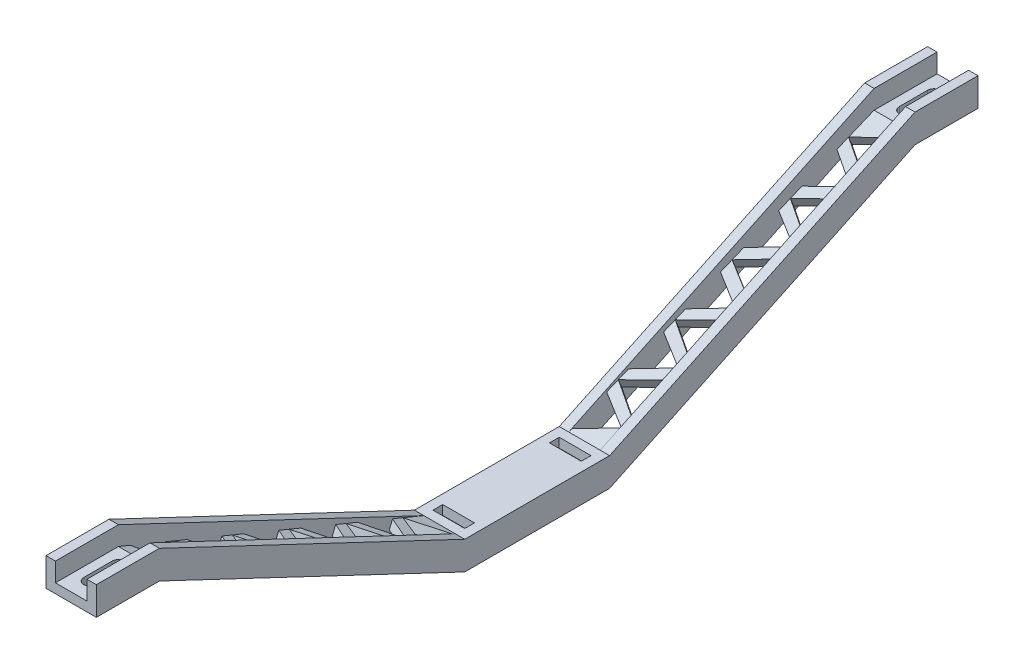
SolidWorks part; units mm, degrees
ref_plane "Front Plane" through (0, 0, 0) normal (0, 0, 1) x (1, 0, 0)
ref_plane "Top Plane" through (0, 0, 0) normal (0, 1, 0) x (1, 0, 0)
ref_plane "Right Plane" through (0, 0, 0) normal (1, 0, 0) x (0, 0, -1)
sketch "BaseSketch" plane through (0, 0, 0) normal (0, 1, 0) x (1, 0, 0)
  line L1 (-8, 150) -> (8, 150)
  line L2 (-8, 150) -> (-8, -150)
  line L3 (-8, -150) -> (8, -150)
  line L4 (8, 150) -> (8, -150)
  line L5 (-8, 150) -> (8, -150) construction
  line L6 (-8, -150) -> (8, 150) construction
  point P0 (0, 0)
  dimension "D1" = 300
  dimension "D2" = 16
extrude "Base" add sketch "BaseSketch" along normal blind 46
sketch "ShapeSketch" plane through (8, 0, 0) normal (1, 0, 0) x (0, 0, -1)
  line L0 (0, 0) -> (0, 3) construction
  line L1 (-23, 3) -> (23, 3)
  line L2 (120, 46) -> (120, 43) construction
  line L4 (-150, 46) -> (150, 46) construction
  line L6 (23, 3) -> (120, 3) construction
  line L7 (23, 3) -> (120, 43)
  line L8 (120, 43) -> (150, 43)
  line L9 (150, 46) -> (150, 0) construction
  line L10 (-23, 3) -> (-120, 3) construction
  line L11 (-120, 46) -> (-120, 43) construction
  line L12 (-23, 3) -> (-120, 43)
  line L13 (-120, 43) -> (-150, 43)
  line L14 (-150, 46) -> (-150, 0) construction
  line L15 (-150, 43) -> (-150, 46)
  line L16 (-150, 46) -> (-120, 46)
  line L17 (-23, 3) -> (-23, 6) construction
  line L18 (-23, 6) -> (23, 6)
  line L19 (23, 3) -> (23, 6) construction
  line L20 (150, 43) -> (150, 46)
  line L21 (150, 46) -> (120, 46)
  line L22 (23, 6) -> (120, 46)
  line L23 (-23, 6) -> (-120, 46)
  point P6 (0, 3)
  dimension "D1" = 3
  dimension "D2" = 46
  dimension "D3" = 97
  dimension "D4" = 3
  dimension "D5" = 30
  dimension "D6" = 97
  dimension "D7" = 3
  dimension "D8" = 30
  dimension "D9" = 3
extrude "Shape" cut sketch "ShapeSketch" against normal through all flip side to cut
sketch "SupportSketch" plane through (-8, 0, 0) normal (-1, 0, 0) x (0, 0, 1)
  line L1 (-150, 52) -> (-150, 43)
  line L5 (-150, 43) -> (-120, 43)
  line L9 (23, 3) -> (23, -3) construction
  line L10 (-23, 3) -> (-23, -3) construction
  line L11 (-120, 43) -> (-23, -3)
  line L12 (23, -3) -> (120, 43)
  line L13 (120, 46) -> (120, 52) construction
  line L15 (150, 46) -> (150, 52) construction
  line L20 (-120, 46) -> (-120, 52) construction
  line L21 (-150, 46) -> (-150, 52) construction
  line L24 (23, -3) -> (-23, -3)
  line L28 (-150, 52) -> (-120, 52)
  line L32 (120, 52) -> (150, 52)
  line L34 (120, 43) -> (150, 43)
  line L35 (-120, 52) -> (-23, 6)
  line L36 (-23, 6) -> (23, 6)
  line L37 (23, 6) -> (120, 52)
  line L38 (150, 43) -> (150, 52)
  dimension "D3" = 6
  dimension "D4" = 6
extrude "SupportR" add sketch "SupportSketch" against normal blind 3 from surface starting at face at (-8, 31.1667, 0)
extrude "SupportL" add sketch "SupportSketch<3>" along normal blind 3 from surface starting at face at (8, 31.1667, 0)
sketch "SupportSketch<3>" plane through (-8, 0, 0) normal (-1, 0, 0) x (0, 0, 1) same geometry as "SupportSketch"
sketch "ConnectionCenterSketch" plane through (0, 6, 0) normal (0, 1, 0) x (1, 0, 0)
  line L1 (0, -18.5) -> (0, 18.5) construction
  line L3 (-5.05, -20.05) -> (5.05, -20.05)
  line L4 (-5.05, -20.05) -> (-5.05, -16.95)
  line L5 (-5.05, -16.95) -> (5.05, -16.95)
  line L6 (5.05, -20.05) -> (5.05, -16.95)
  line L7 (-5.05, -20.05) -> (5.05, -16.95) construction
  line L8 (-5.05, -16.95) -> (5.05, -20.05) construction
  line L9 (-5.05, 16.95) -> (5.05, 16.95)
  line L10 (-5.05, 16.95) -> (-5.05, 20.05)
  line L11 (-5.05, 20.05) -> (5.05, 20.05)
  line L12 (5.05, 16.95) -> (5.05, 20.05)
  line L13 (-5.05, 16.95) -> (5.05, 20.05) construction
  line L14 (-5.05, 20.05) -> (5.05, 16.95) construction
  point P4 (0, 0)
  dimension "D1" = 37
  dimension "D2" = 3.1
  dimension "D3" = 10.1
extrude "ConnectionCenter" cut sketch "ConnectionCenterSketch" against normal through all
sketch "WeightLSketch" plane through (0, -2.9781, 1.2281) normal (0, 0.9245, -0.3812) x (1, 0, 0)
  line L0 (-5, -124.4742) -> (-5, -112.4742)
  line L1 (-5, -130.7616) -> (-5, -23.5504) construction
  line L2 (-5, -23.5504) -> (-5, -128.4742) construction
  line L3 (-5, -112.4742) -> (5, -118.7007)
  line L4 (5, -23.5504) -> (5, -128.4742) construction
  line L5 (5, -118.7007) -> (-5, -124.4742)
  line L6 (-5, -128.4742) -> (5, -128.4742) construction
  line L7 (5, -114.7007) -> (5, -102.7007)
  line L8 (5, -130.7616) -> (5, -23.5504) construction
  line L9 (5, -102.7007) -> (-5, -108.9272)
  line L10 (-5, -108.9272) -> (5, -114.7007)
  line L20 (-5, -104.9272) -> (-5, -92.9272)
  line L21 (-5, -104.9272) -> (5, -99.1537)
  line L22 (5, -99.1537) -> (-5, -92.9272)
  line L23 (5, -95.1537) -> (5, -83.1537)
  line L24 (5, -83.1537) -> (-5, -89.3802)
  line L25 (-5, -89.3802) -> (5, -95.1537)
  line L28 (5, -79.6067) -> (-5, -85.3802)
  line L29 (5, -75.6067) -> (5, -63.6067)
  line L30 (5, -63.6067) -> (-5, -69.8332)
  line L31 (-5, -69.8332) -> (5, -75.6067)
  line L32 (-5, -46.2862) -> (-5, -34.2862)
  line L33 (-5, -34.2862) -> (5, -40.5127)
  line L34 (5, -40.5127) -> (-5, -46.2862)
  line L35 (-5, -85.3802) -> (-5, -73.3802)
  line L36 (-5, -73.3802) -> (5, -79.6067)
  line L37 (-5, -65.8332) -> (-5, -53.8332)
  line L38 (-5, -53.8332) -> (5, -60.0597)
  line L39 (5, -60.0597) -> (-5, -65.8332)
  line L40 (5, -56.0597) -> (5, -44.0597)
  line L41 (5, -44.0597) -> (-5, -50.2862)
  line L42 (-5, -50.2862) -> (5, -56.0597)
  line L43 (5, -36.5127) -> (5, -24.5127)
  line L44 (5, -24.5127) -> (-5, -30.7392)
  line L45 (-5, -30.7392) -> (5, -36.5127)
  dimension "D1" = 12
  dimension "D2" = 60
  dimension "D3" = 4
  dimension "D4" = 4
  dimension "D5" = 12
  dimension "D6" = 60
  dimension "D7" = 4
  dimension "D8" = 12
  dimension "D9" = 60
  dimension "D10" = 4
  dimension "D11" = 60
  dimension "D12" = 12
  dimension "D13" = 4
  dimension "D14" = 12
  dimension "D15" = 60
  dimension "D16" = 4
  dimension "D17" = 12
  dimension "D18" = 60
  dimension "D19" = 4
  dimension "D20" = 12
  dimension "D21" = 60
  dimension "D22" = 4
  dimension "D23" = 60
  dimension "D24" = 12
  dimension "D25" = 4
  dimension "D26" = 60
  dimension "D27" = 12
  dimension "D28" = 4
  dimension "D29" = 12
  dimension "D30" = 60
extrude "WeightL" cut sketch "WeightLSketch" against normal through all
sketch "WeightRSketch" plane through (0, -2.9781, -1.2281) normal (0, 0.9245, 0.3812) x (1, 0, 0)
  line L0 (5, 125.4742) -> (5, 113.4742)
  line L1 (5, 23.5504) -> (5, 130.7616) construction
  line L2 (5, 128.4742) -> (5, 23.5504) construction
  line L3 (5, 113.4742) -> (-5, 119.7007)
  line L4 (-5, 23.5504) -> (-5, 130.7616) construction
  line L5 (-5, 119.7007) -> (5, 125.4742)
  line L6 (-5, 115.7007) -> (-5, 103.7007)
  line L7 (-5, 103.7007) -> (5, 109.4742)
  line L8 (5, 109.4742) -> (-5, 115.7007)
  line L9 (5, 105.4742) -> (5, 93.4742)
  line L10 (5, 93.4742) -> (-5, 99.7007)
  line L11 (-5, 99.7007) -> (5, 105.4742)
  line L12 (-5, 95.7007) -> (-5, 83.7007)
  line L13 (-5, 83.7007) -> (5, 89.9272)
  line L14 (5, 89.9272) -> (-5, 95.7007)
  line L15 (5, 85.9272) -> (5, 73.9272)
  line L16 (5, 73.9272) -> (-5, 79.7007)
  line L17 (-5, 79.7007) -> (5, 85.9272)
  line L18 (-5, 75.7007) -> (-5, 63.7007)
  line L19 (-5, 128.4742) -> (-5, 23.5504) construction
  line L20 (-5, 63.7007) -> (5, 69.9272)
  line L21 (5, 69.9272) -> (-5, 75.7007)
  line L22 (5, 65.9272) -> (5, 53.9272)
  line L23 (5, 53.9272) -> (-5, 60.1537)
  line L24 (-5, 60.1537) -> (5, 65.9272)
  line L25 (-5, 56.1537) -> (-5, 44.1537)
  line L26 (-5, 44.1537) -> (5, 50.3802)
  line L27 (5, 50.3802) -> (-5, 56.1537)
  line L28 (5, 46.3802) -> (5, 34.3802)
  line L29 (5, 34.3802) -> (-5, 40.6067)
  line L30 (-5, 40.6067) -> (5, 46.3802)
  line L31 (-5, 36.6067) -> (-5, 24.6067)
  line L32 (-5, 36.6067) -> (5, 30.8332)
  line L33 (5, 30.8332) -> (-5, 24.6067)
  dimension "D1" = 3
  dimension "D2" = 12
  dimension "D3" = 60
  dimension "D4" = 60
  dimension "D5" = 4
  dimension "D6" = 12
  dimension "D7" = 4
  dimension "D8" = 12
  dimension "D9" = 60
  dimension "D10" = 4
  dimension "D11" = 12
  dimension "D12" = 60
  dimension "D13" = 4
  dimension "D14" = 12
  dimension "D15" = 60
  dimension "D16" = 4
  dimension "D17" = 12
  dimension "D18" = 60
  dimension "D19" = 4
  dimension "D20" = 12
  dimension "D21" = 60
  dimension "D22" = 4
  dimension "D23" = 60
  dimension "D24" = 12
  dimension "D25" = 4
  dimension "D26" = 12
  dimension "D27" = 60
  dimension "D28" = 4
  dimension "D29" = 12
  dimension "D30" = 60
extrude "WeightR" cut sketch "WeightRSketch" against normal through all
sketch "ConnectionEndSketch" plane through (0, 46, 0) normal (0, 1, 0) x (1, 0, 0)
  line L0 (0, -150) -> (0, -134) construction
  line L3 (-5, -150) -> (5, -150) construction
  line L4 (0, -120) -> (0, -125) construction
  line L7 (0, 150) -> (0, 134) construction
  line L8 (5, 150) -> (-5, 150) construction
  line L9 (0, 120) -> (0, 125) construction
  line L10 (-5, 120) -> (5, 120) construction
  line L11 (0, 134) -> (0, 125) construction
  line L12 (2, 134) -> (2, 125)
  line L13 (-2, 134) -> (-2, 125)
  line L14 (-5, -120) -> (5, -120) construction
  line L15 (0, -134) -> (0, -125) construction
  line L16 (-2, -134) -> (-2, -125)
  line L17 (2, -134) -> (2, -125)
  arc A2 (2, 134) -> (-2, 134) centre (0, 134) ccw
  arc A3 (-2, 125) -> (2, 125) centre (0, 125) ccw
  arc A4 (-2, -134) -> (2, -134) centre (0, -134) ccw
  arc A5 (2, -125) -> (-2, -125) centre (0, -125) ccw
  point P8 (0, -129.5)
  point P22 (0, 129.5)
  dimension "D1" = 16
  dimension "D2" = 5
  dimension "D3" = 4
  dimension "D5" = 16
  dimension "D6" = 5
  dimension "D7" = 4
extrude "ConnectionEnd" cut sketch "ConnectionEndSketch" against normal through all and the other way through all
sketch "ShortnerSketch" plane through (-8, 0, 0) normal (-1, 0, 0) x (0, 0, 1)
  line L0 (-140, 0) -> (140, 0) construction
  line L2 (-140, 0) -> (-157.7345, 0)
  line L3 (-140, 0) -> (-140, 84.1236)
  line L4 (-140, 84.1236) -> (-157.7345, 84.1236)
  line L5 (-157.7345, 0) -> (-157.7345, 84.1236)
  line L6 (140, 0) -> (167.514, 0)
  line L7 (140, 0) -> (140, 94.2186)
  line L8 (140, 94.2186) -> (167.514, 94.2186)
  line L9 (167.514, 0) -> (167.514, 94.2186)
  point P4 (0, 0)
  dimension "D1" = 280
extrude "Cut-Extrude1" cut sketch "ShortnerSketch" against normal through all
